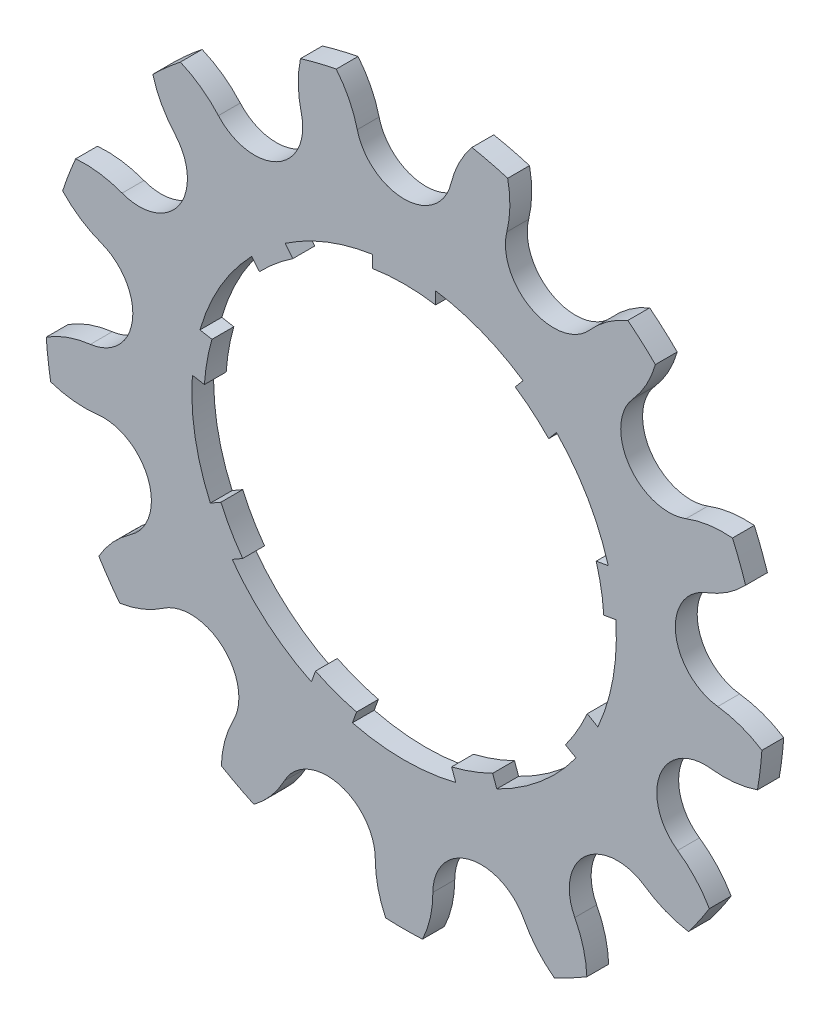
SolidWorks part; units mm, degrees
ref_plane "Alzado" through (0, 0, 0) normal (0, 0, 1) x (1, 0, 0)
ref_plane "Planta" through (0, 0, 0) normal (0, 1, 0) x (1, 0, 0)
ref_plane "Vista lateral" through (0, 0, 0) normal (1, 0, 0) x (0, 0, -1)
sketch "Sk_Disco" plane through (0, 0, 0) normal (0, 0, 1) x (1, 0, 0)
  line L0 (2.6, 17.3058) -> (2.6, 16.2939)
  line L1 (-2.6, 16.2939) -> (-2.6, 17.3058)
  line L2 (-9.8102, 14.4917) -> (-9.1638, 13.7213)
  line L3 (-11.9216, 11.4073) -> (-12.568, 12.1777)
  line L4 (-16.8302, 4.7954) -> (-15.8398, 4.6207)
  line L5 (-16.4649, 1.0754) -> (-17.4553, 1.2501)
  line L6 (-15.9751, -7.1447) -> (-15.1041, -6.6419)
  line L7 (-13.3041, -9.7596) -> (-14.1751, -10.2624)
  line L8 (-7.6451, -15.7418) -> (-7.3011, -14.7968)
  line L9 (-3.9182, -16.028) -> (-4.2622, -16.973)
  line L10 (4.2622, -16.973) -> (3.9182, -16.028)
  line L11 (7.3011, -14.7968) -> (7.6451, -15.7418)
  line L12 (14.1751, -10.2624) -> (13.3041, -9.7596)
  line L13 (15.1041, -6.6419) -> (15.9751, -7.1447)
  line L14 (17.4553, 1.2501) -> (16.4649, 1.0754)
  line L15 (15.8398, 4.6207) -> (16.8302, 4.7954)
  line L16 (12.568, 12.1777) -> (11.9216, 11.4073)
  line L17 (9.1638, 13.7213) -> (9.8102, 14.4917)
  circle A0 centre (0, 0) radius 29.573
  arc A1 (2.6, 16.2939) -> (-2.6, 16.2939) centre (0, 0) ccw
  arc A2 (-2.6, 17.3058) -> (-9.8102, 14.4917) centre (0, 0) ccw
  arc A3 (-9.1638, 13.7213) -> (-11.9216, 11.4073) centre (0, 0) ccw
  arc A4 (-12.568, 12.1777) -> (-16.8302, 4.7954) centre (0, 0) ccw
  arc A5 (-15.8398, 4.6207) -> (-16.4649, 1.0754) centre (0, 0) ccw
  arc A6 (-17.4553, 1.2501) -> (-15.9751, -7.1447) centre (0, 0) ccw
  arc A7 (-15.1041, -6.6419) -> (-13.3041, -9.7596) centre (0, 0) ccw
  arc A8 (-14.1751, -10.2624) -> (-7.6451, -15.7418) centre (0, 0) ccw
  arc A9 (-7.3011, -14.7968) -> (-3.9182, -16.028) centre (0, 0) ccw
  arc A10 (-4.2622, -16.973) -> (4.2622, -16.973) centre (0, 0) ccw
  arc A11 (3.9182, -16.028) -> (7.3011, -14.7968) centre (0, 0) ccw
  arc A12 (7.6451, -15.7418) -> (14.1751, -10.2624) centre (0, 0) ccw
  arc A13 (13.3041, -9.7596) -> (15.1041, -6.6419) centre (0, 0) ccw
  arc A14 (15.9751, -7.1447) -> (17.4553, 1.2501) centre (0, 0) ccw
  arc A15 (16.4649, 1.0754) -> (15.8398, 4.6207) centre (0, 0) ccw
  arc A16 (16.8302, 4.7954) -> (12.568, 12.1777) centre (0, 0) ccw
  arc A17 (11.9216, 11.4073) -> (9.1638, 13.7213) centre (0, 0) ccw
  arc A18 (9.8102, 14.4917) -> (2.6, 17.3058) centre (0, 0) ccw
  dimension "D1" = 59.1459
extrude "Disco" add sketch "Sk_Disco" along normal blind 1.8
sketch "Sk_Hueco" plane through (0, 0, 0) normal (0, 0, 1) x (1, 0, 0)
  line L0 (0, 0) -> (0, 26.534) construction
  line L1 (0, 0) -> (-12.331, 23.4947) construction
  line L2 (0, 0) -> (12.331, 23.4947) construction
  line L3 (0, 26.534) -> (-12.331, 23.4947) construction
  line L4 (0, 26.534) -> (12.331, 23.4947) construction
  arc A0 (-3.8595, 25.5827) -> (3.8595, 25.5827) centre (0, 26.534) ccw
  arc A1 (-3.8595, 25.5827) -> (-7.4009, 30.6933) centre (-12.331, 23.4947) ccw
  arc A2 (7.4009, 30.6933) -> (3.8595, 25.5827) centre (12.331, 23.4947) ccw
  arc A3 (7.4009, 30.6933) -> (-7.4009, 30.6933) centre (0, 0) ccw
  dimension "D6" = 3.975
  dimension "D7" = 31.573
  dimension "D1" = 26.534
  dimension "D2" = 26.534
  dimension "D3" = 26.534
  dimension "D4" = 27.692
  dimension "D5" = 27.692
extrude "Hueco_diente" cut sketch "Sk_Hueco" along normal through all
ref_axis "Eje_pinon" through (0, 0, -0.09) along (0, 0, 1)
pattern_circular "Matriz_dientes" count 13 over 360 about axis through (0, 0, -0.09) along (0, 0, 1) of "Hueco_diente"
equation "\"Z\"= 13"
equation "\"p\"= 12.7"
equation "\"Dr\"= 7.75"
equation "\"e\"= 1.8"
equation "\"D\"= \"p\" / sin ( 180 / \"Z\" )"
equation "\"De\"= \"p\" * ( 0.6 + 1 / tan ( 180 / \"Z\" ) )"
equation "\"Di\"= \"D\" - \"Dr\""
equation "\"Ang\"= 360 / \"Z\""
equation "\"D1@Sk_Disco\" = \"De\""
equation "\"D1@Disco\" = \"e\""
equation "\"D1@Sk_Hueco\" = \"D\" / 2"
equation "\"D2@Sk_Hueco\" = \"D\" / 2"
equation "\"D3@Sk_Hueco\" = \"D\" / 2"
equation "\"D4@Sk_Hueco\" = \"Ang\""
equation "\"D5@Sk_Hueco\" = \"Ang\""
equation "\"D6@Sk_Hueco\" = \"Dr\" / 2 + 0.1"
equation "\"D7@Sk_Hueco\" = \"De\" / 2 + 2"
equation "\"D1@Matriz_dientes\" = \"Z\""
